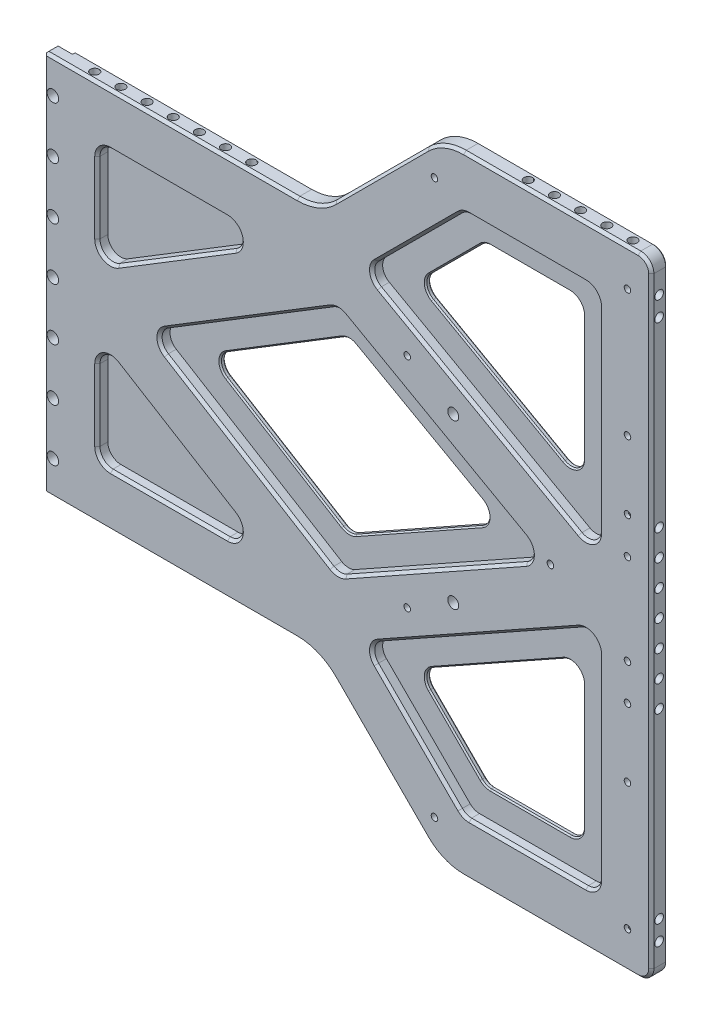
SolidWorks part; units mm, degrees
material "6061 合金"
ref_plane "前视基准面" through (0, 0, 0) normal (0, 0, 1) x (1, 0, 0)
ref_plane "上视基准面" through (0, 0, 0) normal (0, 1, 0) x (1, 0, 0)
ref_plane "右视基准面" through (0, 0, 0) normal (1, 0, 0) x (0, 0, -1)
sketch "草图1" plane through (0, 0, 0) normal (0, 0, 1) x (1, 0, 0)
  line L0 (11.5, -73) -> (-13.5, -73) construction
  line L1 (11.5, 73) -> (110.1759, 73)
  line L2 (11.5, 73) -> (11.5, -73)
  line L3 (11.5, -73) -> (110.1759, -73)
  line L5 (387.1759, 0) -> (237.1759, 0) construction
  line L6 (-812.8241, 0) -> (387.1759, 0) construction
  line L7 (237.1759, 120) -> (237.1759, -120)
  line L8 (237.1759, 120) -> (157.1759, 120)
  line L11 (237.1759, -120) -> (157.1759, -120)
  line L12 (157.1759, 120) -> (110.1759, 73)
  line L13 (157.1759, -120) -> (110.1759, -73)
  point P10 (237.1759, 0)
  point P15 (237.1759, 0)
extrude "凸台-拉伸1" add sketch "草图1" against normal blind 1
sketch "草图2" plane through (0, 0, 0) normal (0, 0, 1) x (1, 0, 0)
  line L0 (11.5, 73) -> (5.5, 73)
  line L1 (5.5, 73) -> (5.5, -73)
  line L2 (5.5, -73) -> (11.5, -73)
  line L8 (11.5, 73) -> (11.5, -73)
  line L9 (11.5, -73) -> (110.1759, -73)
  line L10 (110.1759, -73) -> (157.1759, -120)
  line L11 (157.1759, -120) -> (237.1759, -120)
  line L12 (237.1759, -120) -> (237.1759, 120)
  line L13 (237.1759, 120) -> (157.1759, 120)
  line L14 (157.1759, 120) -> (110.1759, 73)
  line L15 (110.1759, 73) -> (11.5, 73)
  line L16 (11.5, 73) -> (11.5, -73) construction
  line L17 (11.5, -73) -> (110.1759, -73)
  line L18 (110.1759, -73) -> (157.1759, -120)
  line L19 (157.1759, -120) -> (237.1759, -120)
  line L20 (237.1759, -120) -> (237.1759, 120)
  line L21 (237.1759, 120) -> (157.1759, 120)
  line L22 (157.1759, 120) -> (110.1759, 73)
  line L23 (110.1759, 73) -> (11.5, 73)
  dimension "D1" = 0
extrude "凸台-拉伸2" add sketch "草图2" along normal blind 5
fillet "圆角1" radius 20 4 edges at (157.1759, 120, 2) (157.1759, -120, 2) (110.1759, -73, 2) (110.1759, 73, 2)
sketch "草图3" plane through (0, 0, 5) normal (0, 0, 1) x (1, 0, 0)
  line L8 (217.1759, 0) -> (117.1989, 56.0448) construction
  line L9 (217.1759, 0) -> (117.1989, -56.0448) construction
  line L11 (25.5, 0) -> (117.1989, 56.0448) construction
  line L12 (25.5, 0) -> (117.1989, -56.0448) construction
  line L13 (237.6263, 0) -> (116.9806, 67.6312)
  line L14 (6.3243, 0) -> (116.9806, 67.6312)
  line L15 (6.3243, 0) -> (116.9806, -67.6312)
  line L16 (217.1759, 100) -> (165.4601, 100)
  line L17 (165.4601, 100) -> (130.1759, 64.7157)
  line L18 (101.8916, 53) -> (25.5, 53)
  line L19 (25.5, 53) -> (25.5, -53)
  line L20 (25.5, -53) -> (101.8916, -53)
  line L21 (130.1759, -64.7157) -> (165.4601, -100)
  line L22 (165.4601, -100) -> (217.1759, -100)
  line L23 (217.1759, -100) -> (217.1759, 100)
  line L24 (217.1759, 100) -> (165.4601, 100)
  line L25 (165.4601, 100) -> (130.1759, 64.7157)
  line L26 (101.8916, 53) -> (25.5, 53)
  line L27 (25.5, 53) -> (25.5, -53)
  line L28 (25.5, -53) -> (101.8916, -53)
  line L29 (130.1759, -64.7157) -> (165.4601, -100)
  line L30 (165.4601, -100) -> (217.1759, -100)
  line L31 (217.1759, -100) -> (217.1759, 100)
  line L32 (237.6263, 0) -> (116.9806, -67.6312)
  line L33 (196.7254, 0) -> (117.4172, 44.4584)
  line L34 (44.6757, 0) -> (117.4172, 44.4584)
  line L35 (44.6757, 0) -> (117.4172, -44.4584)
  line L36 (196.7254, 0) -> (117.4172, -44.4584)
  arc A8 (101.8916, 53) -> (130.1759, 64.7157) centre (101.8916, 93) ccw
  arc A9 (130.1759, -64.7157) -> (101.8916, -53) centre (101.8916, -93) ccw
  arc A10 (101.8916, 53) -> (130.1759, 64.7157) centre (101.8916, 93) ccw
  arc A11 (130.1759, -64.7157) -> (101.8916, -53) centre (101.8916, -93) ccw
  dimension "D2" = 10
  dimension "D1" = 20
  dimension "D3" = 10
extrude "切除-拉伸1" cut sketch "草图3" against normal blind 4 contours L36 L33 L34 L35 | A10 L13 L31 L24 L25 | A11 L29 L30 L31 L32 | L27 L28 L15 | L26 L27 L14 region at (183.7899, 63.6338, 5) region at (183.7899, -63.6338, 5) region at (48.0138, 39.2399, 5) region at (48.0138, -39.2399, 5) region at (119.6061, 0, 5)
fillet "圆角2" radius 5 18 edges at (165.4601, -100, 3) (217.1759, -100, 3) (217.1759, -11.4641, 3) (127.1113, -61.9522, 3) (217.1759, 11.4641, 3) (165.4601, 100, 3) (127.1113, 61.9522, 3) (117.4172, 44.4584, 3) (44.6757, 0, 3) (117.4172, -44.4584, 3) (196.7254, 0, 3) (25.5, -53, 3) (93.0414, -53, 3) (25.5, -11.7198, 3) (25.5, 53, 3) (25.5, 11.7198, 3) (93.0414, 53, 3) (217.1759, 100, 3)
sketch "草图4" plane through (0, 0, 1) normal (0, 0, 1) x (1, 0, 0)
  line L8 (176.275, 0) -> (117.6355, 32.872)
  line L9 (117.6355, 32.872) -> (63.8513, 0)
  line L10 (63.8513, 0) -> (117.6355, -32.872)
  line L11 (117.6355, -32.872) -> (176.275, 0)
  line L12 (176.275, 0) -> (117.6355, 32.872)
  line L13 (117.6355, 32.872) -> (63.8513, 0)
  line L14 (63.8513, 0) -> (117.6355, -32.872)
  line L15 (117.6355, -32.872) -> (176.275, 0)
  line L19 (143.7124, 64.1101) -> (207.1759, 28.5339)
  line L20 (207.1759, 28.5339) -> (207.1759, 90)
  line L21 (207.1759, 90) -> (169.6023, 90)
  line L22 (169.6023, 90) -> (143.7124, 64.1101)
  line L23 (143.7124, 64.1101) -> (207.1759, 28.5339)
  line L24 (207.1759, 28.5339) -> (207.1759, 90)
  line L25 (207.1759, 90) -> (169.6023, 90)
  line L26 (169.6023, 90) -> (143.7124, 64.1101)
  line L31 (143.7124, -64.1101) -> (169.6023, -90)
  line L32 (169.6023, -90) -> (207.1759, -90)
  line L33 (207.1759, -90) -> (207.1759, -28.5339)
  line L34 (207.1759, -28.5339) -> (143.7124, -64.1101)
  line L35 (143.7124, -64.1101) -> (169.6023, -90)
  line L36 (169.6023, -90) -> (207.1759, -90)
  line L37 (207.1759, -90) -> (207.1759, -28.5339)
  line L38 (207.1759, -28.5339) -> (143.7124, -64.1101)
  dimension "D1" = 10
  dimension "D2" = 10
  dimension "D3" = 10
extrude "切除-拉伸2" cut sketch "草图4" against normal blind 5
fillet "圆角3" radius 5 12 edges at (63.8513, 0, 0) (117.6355, 32.872, 0) (176.275, 0, 0) (117.6355, -32.872, 0) (207.1759, 90, 0) (207.1759, 28.5339, 0) (169.6023, 90, 0) (207.1759, -90, 0) (169.6023, -90, 0) (143.7124, -64.1101, 0) (207.1759, -28.5339, 0) (143.7124, 64.1101, 0)
fillet "圆角4" radius 5 2 edges at (237.1759, 120, 2) (237.1759, -120, 2)
chamfer "倒角1" distance 1 angle 45 36 edges at (26.9645, 51.5355, 5) (25.5, 34.3178, 5) (52.8864, 53, 5) (28.0543, 16.2746, 5) (80.0858, 49.3544, 5) (55.4938, 30.0516, 5) (26.9645, -51.5355, 5) (25.5, -34.3178, 5) (52.8864, -53, 5) (28.0543, -16.2746, 5) (80.0858, -49.3544, 5) (55.4938, -30.0516, 5) (49.2635, 0, 5) (83.2874, 23.5989, 5) (83.2874, -23.5989, 5) (117.4322, 43.6643, 5) (117.4322, -43.6643, 5) (154.4582, 23.694, 5) (154.4582, -23.694, 5) (191.5002, 0, 5) (165.6178, -99.6194, 5) (147.9842, -82.5241, 5) (189.8535, -100, 5) (130.5553, -62.2931, 5) (215.7114, -98.5355, 5) (171.3971, -37.1266, 5) (217.1759, -57.4995, 5) (214.7032, -15.6848, 5) (171.3971, 37.1266, 5) (214.7032, 15.6848, 5) (130.5553, 62.2931, 5) (217.1759, 57.4995, 5) (147.9842, 82.5241, 5) (215.7114, 98.5355, 5) (165.6178, 99.6194, 5) (189.8535, 100, 5)
chamfer "倒角2" distance 1 angle 45 13 edges at (53.6958, 73, 5) (109.5453, 74.5224, 5) (133.6759, 96.5, 5) (53.6958, -73, 5) (157.8065, 118.4776, 5) (109.5453, -74.5224, 5) (198.818, 120, 5) (133.6759, -96.5, 5) (235.7114, 118.5355, 5) (157.8065, -118.4776, 5) (237.1759, 0, 5) (198.818, -120, 5) (235.7114, -118.5355, 5)
sketch "草图5" plane through (0, 0, 5) normal (0, 0, 1) x (1, 0, 0)
  circle A0 centre (8.5, 60) radius 2.2
  circle A1 centre (8.5, 40) radius 2.2
  circle A2 centre (8.5, 20) radius 2.2
  circle A3 centre (8.5, 0) radius 2.2
  circle A4 centre (8.5, -20) radius 2.2
  circle A5 centre (8.5, -40) radius 2.2
  circle A6 centre (8.5, -60) radius 2.2
  point P0 (8.5, 60)
  point P1 (8.5, 40)
  point P3 (8.5, 20)
  point P5 (8.5, 0)
  point P7 (8.5, -20)
  point P9 (8.5, -40)
  point P11 (8.5, -60)
  dimension "D1" = 7
extrude "切除-拉伸3" cut sketch "草图5" against normal through all both and the other way through all
hole_wizard "M4 螺纹孔1" positions "草图7" profile "草图8" tap size "M4" standard "GB"
sketch "草图7" plane through (0, -73, 0) normal (0, -1, 0) x (-1, 0, 0)
  point P0 (-81.5, -2)
  point P3 (-71.5, -2)
  point P6 (-61.5, -2)
  point P9 (-51.5, -2)
  point P12 (-41.5, -2)
  point P15 (-31.5, -2)
  point P18 (-21.5, -2)
sketch "草图8" plane through (81.5, -73, 2) normal (1, 0, 0) x (0, 0, -1)
  line L0 (0, 0) -> (0, 11.0914)
  line L1 (0, 11.0914) -> (1.65, 10.1)
  line L2 (1.65, 10.1) -> (1.65, 0)
  line L5 (1.65, 0) -> (0, 0)
  line L10 (0, 11.0914) -> (-1.65, 10.1) construction
  line L11 (0, -6.35) -> (0, 107.95) construction
  dimension "螺纹孔钻头直径" = 3.3
  dimension "螺纹孔钻头深度" = 10.1
  dimension "导头角度" = 118
cosmetic thread "孔螺蚊线1" parameters "D1"=8, "D2"=4
cosmetic thread "孔螺蚊线2" parameters "D1"=8, "D2"=4
cosmetic thread "孔螺蚊线3" parameters "D1"=8, "D2"=4
cosmetic thread "孔螺蚊线4" parameters "D1"=8, "D2"=4
cosmetic thread "孔螺蚊线5" parameters "D1"=8, "D2"=4
cosmetic thread "孔螺蚊线6" parameters "D1"=8, "D2"=4
cosmetic thread "孔螺蚊线7" parameters "D1"=8, "D2"=4
mirror "镜向1" about plane through (0, 0, 0) normal (0, 1, 0) of "M4 螺纹孔1"
cosmetic thread "孔螺蚊线8" parameters "D1"=8, "D2"=4
cosmetic thread "孔螺蚊线9" parameters "D1"=8, "D2"=4
cosmetic thread "孔螺蚊线10" parameters "D1"=8, "D2"=4
cosmetic thread "孔螺蚊线11" parameters "D1"=8, "D2"=4
cosmetic thread "孔螺蚊线12" parameters "D1"=8, "D2"=4
cosmetic thread "孔螺蚊线13" parameters "D1"=8, "D2"=4
cosmetic thread "孔螺蚊线14" parameters "D1"=8, "D2"=4
hole_wizard "M4 螺纹孔2" positions "草图10" profile "草图11" tap size "M4" standard "GB"
sketch "草图10" plane through (0, -120, 0) normal (0, -1, 0) x (-1, 0, 0)
  point P0 (-227.1759, -2)
  point P3 (-217.1759, -2)
  point P6 (-207.1759, -2)
  point P9 (-197.1759, -2)
  point P12 (-187.1759, -2)
sketch "草图11" plane through (227.1759, -120, 2) normal (1, 0, 0) x (0, 0, -1)
  line L0 (0, 0) -> (0, 11.0914)
  line L1 (0, 11.0914) -> (1.65, 10.1)
  line L2 (1.65, 10.1) -> (1.65, 0)
  line L5 (1.65, 0) -> (0, 0)
  line L10 (0, 11.0914) -> (-1.65, 10.1) construction
  line L11 (0, -6.35) -> (0, 107.95) construction
  dimension "螺纹孔钻头直径" = 3.3
  dimension "螺纹孔钻头深度" = 10.1
  dimension "导头角度" = 118
cosmetic thread "孔螺蚊线15" parameters "D1"=8, "D2"=4
cosmetic thread "孔螺蚊线16" parameters "D1"=8, "D2"=4
cosmetic thread "孔螺蚊线17" parameters "D1"=8, "D2"=4
cosmetic thread "孔螺蚊线18" parameters "D1"=8, "D2"=4
cosmetic thread "孔螺蚊线19" parameters "D1"=8, "D2"=4
mirror "镜向2" about plane through (0, 0, 0) normal (0, 1, 0) of "M4 螺纹孔2"
cosmetic thread "孔螺蚊线20" parameters "D1"=8, "D2"=4
cosmetic thread "孔螺蚊线21" parameters "D1"=8, "D2"=4
cosmetic thread "孔螺蚊线22" parameters "D1"=8, "D2"=4
cosmetic thread "孔螺蚊线23" parameters "D1"=8, "D2"=4
cosmetic thread "孔螺蚊线24" parameters "D1"=8, "D2"=4
hole_wizard "M4 螺纹孔3" positions "草图13" profile "草图14" tap size "M4" standard "GB"
sketch "草图13" plane through (237.1759, 0, 0) normal (1, 0, 0) x (0, 0, -1)
  point P0 (-2, -99.5)
  point P3 (-2, -107)
sketch "草图14" plane through (237.1759, -99.5, 2) normal (0, 1, 0) x (0, 0, -1)
  line L0 (0, 0) -> (0, 11.0914)
  line L1 (0, 11.0914) -> (1.65, 10.1)
  line L2 (1.65, 10.1) -> (1.65, 0)
  line L5 (1.65, 0) -> (0, 0)
  line L10 (0, 11.0914) -> (-1.65, 10.1) construction
  line L11 (0, -6.35) -> (0, 107.95) construction
  dimension "螺纹孔钻头直径" = 3.3
  dimension "螺纹孔钻头深度" = 10.1
  dimension "导头角度" = 118
cosmetic thread "孔螺蚊线26" parameters "D1"=8, "D2"=4
cosmetic thread "孔螺蚊线27" parameters "D1"=8, "D2"=4
mirror "镜向3" about plane through (0, 0, 0) normal (0, 1, 0) of "M4 螺纹孔3"
cosmetic thread "孔螺蚊线28" parameters "D1"=8, "D2"=4
cosmetic thread "孔螺蚊线29" parameters "D1"=8, "D2"=4
sketch "草图15" plane through (0, 0, 5) normal (0, 0, 1) x (1, 0, 0)
  line L0 (151.5, 0) -> (161.5, 0) construction
  line L1 (151.5, 70) -> (151.5, -70) construction
  line L2 (-812.8241, 0) -> (387.1759, 0) construction
  line L3 (133.4954, -36.5917) -> (142.2972, -52.293) construction
  line L4 (189.4341, -5.2337) -> (120.4603, -43.8989) construction
  line L5 (132.5744, -57.7433) -> (209.2419, -14.7652) construction
  line L6 (89.7964, -71.4061) -> (185.9962, -17.4786) construction
  line L7 (161.5, 31.2106) -> (161.5, -31.2106) construction
  point P15 (137.8963, -44.4423)
  point P18 (161.5, 0)
hole_wizard "M5 螺纹孔1" positions "草图16" profile "草图17" tap size "M5" standard "GB"
sketch "草图16" plane through (0, 0, 5) normal (0, 0, 1) x (1, 0, 0)
  point P0 (161.5, 31.2106)
  point P3 (161.5, -31.2106)
sketch "草图17" plane through (161.5, 31.2106, 5) normal (1, 0, 0) x (0, -1, 0)
  line L0 (0, 0) -> (0, 13.6618)
  line L1 (0, 13.6618) -> (2.1, 12.4)
  line L2 (2.1, 12.4) -> (2.1, 0)
  line L5 (2.1, 0) -> (0, 0)
  line L10 (0, 13.6618) -> (-2.1, 12.4) construction
  line L11 (0, -6.35) -> (0, 107.95) construction
  dimension "螺纹孔钻头直径" = 4.2
  dimension "螺纹孔钻头深度" = 12.4
  dimension "导头角度" = 118
cosmetic thread "孔螺蚊线30" parameters "D1"=10, "D2"=5
cosmetic thread "孔螺蚊线31" parameters "D1"=10, "D2"=5
sketch "草图18" plane through (237.1759, 0, 0) normal (1, 0, 0) x (0, 0, -1)
  line L0 (1, 0) -> (-5, 0) construction
  line L1 (1, -115) -> (1, 115) construction
  line L2 (-2, 10) -> (-2, -10) construction
  line L3 (-2, 20) -> (-2, -20) construction
  line L4 (-2, 30) -> (-2, -30) construction
  point P8 (-2, 0)
  point P12 (-2, 0)
  point P15 (-2, 0)
hole_wizard "M4 螺纹孔4" positions "草图19" profile "草图20" tap size "M4" standard "GB"
sketch "草图19" plane through (237.1759, 0, 0) normal (1, 0, 0) x (0, 0, -1)
  line L0 (-2, 10) -> (-2, -10) construction
  point P0 (-2, 30)
  point P3 (-2, 20)
  point P6 (-2, 10)
  point P9 (-2, 0)
  point P13 (-2, -10)
  point P16 (-2, -20)
  point P19 (-2, -30)
sketch "草图20" plane through (237.1759, 30, 2) normal (0, 1, 0) x (0, 0, -1)
  line L0 (0, 0) -> (0, 11.0914)
  line L1 (0, 11.0914) -> (1.65, 10.1)
  line L2 (1.65, 10.1) -> (1.65, 0)
  line L5 (1.65, 0) -> (0, 0)
  line L10 (0, 11.0914) -> (-1.65, 10.1) construction
  line L11 (0, -6.35) -> (0, 107.95) construction
  dimension "螺纹孔钻头直径" = 3.3
  dimension "螺纹孔钻头深度" = 10.1
  dimension "导头角度" = 118
cosmetic thread "孔螺蚊线32" parameters "D1"=8, "D2"=4
cosmetic thread "孔螺蚊线33" parameters "D1"=8, "D2"=4
cosmetic thread "孔螺蚊线34" parameters "D1"=8, "D2"=4
cosmetic thread "孔螺蚊线35" parameters "D1"=8, "D2"=4
cosmetic thread "孔螺蚊线36" parameters "D1"=8, "D2"=4
cosmetic thread "孔螺蚊线37" parameters "D1"=8, "D2"=4
cosmetic thread "孔螺蚊线38" parameters "D1"=8, "D2"=4
sketch "草图21" plane through (0, 0, 5) normal (0, 0, 1) x (1, 0, 0)
  line L0 (161.5, -31.2106) -> (143.9, -31.2106)
  line L1 (143.9, -31.2106) -> (143.9, -41.7006)
  line L3 (161.5, -31.2106) -> (161.5, -105.8306)
  line L4 (161.5, -105.8306) -> (154.33, -105.8306)
  line L5 (161.5, -31.2106) -> (198.64, -31.2106)
  line L6 (198.64, -31.2106) -> (198.64, -0.0706)
  line L7 (228.08, -31.2106) -> (228.08, -17.3206)
  line L8 (198.64, -31.2106) -> (228.08, -31.2106)
  line L9 (228.08, -31.2106) -> (228.08, -57.3206)
  line L10 (228.08, -57.3206) -> (228.08, -105.8406)
hole_wizard "M3 螺纹孔1" positions "草图22" profile "草图23" tap size "M3" standard "GB"
sketch "草图22" plane through (0, 0, 5) normal (0, 0, 1) x (1, 0, 0)
  point P0 (143.9, -41.7006)
  point P3 (154.33, -105.8306)
  point P6 (198.64, 0.0706)
  point P8 (228.08, -31.2106)
  point P11 (228.08, -17.3206)
  point P14 (228.08, -105.8406)
  point P17 (228.08, -57.3206)
sketch "草图23" plane through (143.9, -41.7006, 5) normal (1, 0, 0) x (0, -1, 0)
  line L0 (0, 0) -> (0, 8.2511)
  line L1 (0, 8.2511) -> (1.25, 7.5)
  line L2 (1.25, 7.5) -> (1.25, 0)
  line L5 (1.25, 0) -> (0, 0)
  line L10 (0, 8.2511) -> (-1.25, 7.5) construction
  line L11 (0, -6.35) -> (0, 107.95) construction
  dimension "螺纹孔钻头直径" = 2.5
  dimension "螺纹孔钻头深度" = 7.5
  dimension "导头角度" = 118
cosmetic thread "孔螺蚊线39" parameters "D1"=6, "D2"=3
cosmetic thread "孔螺蚊线40" parameters "D1"=6, "D2"=3
cosmetic thread "孔螺蚊线41" parameters "D1"=6, "D2"=3
cosmetic thread "孔螺蚊线42" parameters "D1"=6, "D2"=3
cosmetic thread "孔螺蚊线43" parameters "D1"=6, "D2"=3
cosmetic thread "孔螺蚊线44" parameters "D1"=6, "D2"=3
cosmetic thread "孔螺蚊线45" parameters "D1"=6, "D2"=3
mirror "镜向4" about plane through (0, 0, 0) normal (0, 1, 0) of "M3 螺纹孔1"
cosmetic thread "孔螺蚊线46" parameters "D1"=6, "D2"=3
cosmetic thread "孔螺蚊线47" parameters "D1"=6, "D2"=3
cosmetic thread "孔螺蚊线48" parameters "D1"=6, "D2"=3
cosmetic thread "孔螺蚊线49" parameters "D1"=6, "D2"=3
cosmetic thread "孔螺蚊线50" parameters "D1"=6, "D2"=3
cosmetic thread "孔螺蚊线51" parameters "D1"=6, "D2"=3
cosmetic thread "孔螺蚊线52" parameters "D1"=6, "D2"=3
chamfer "倒角3" distance 0.5 angle 45 48 edges at (92.9844, -17.8057, -1) (117.6504, -32.0779, -1) (68.4391, 0, -1) (144.3421, -17.9008, -1) (92.9844, 17.8057, -1) (171.0497, 0, -1) (117.6504, 32.0779, -1) (144.3421, 17.9008, -1) (92.9844, -17.8057, 1) (117.6504, -32.0779, 1) (68.4391, 0, 1) (144.3421, -17.9008, 1) (92.9844, 17.8057, 1) (171.0497, 0, 1) (117.6504, 32.0779, 1) (144.3421, 17.9008, 1) (146.9635, 64.5591, 1) (158.2594, 78.6571, 1) (174.6012, 46.7945, 1) (169.7599, 89.6194, 1) (204.7032, 32.7546, 1) (186.9246, 90, 1) (207.1759, 61.0344, 1) (205.7114, 88.5355, 1) (146.9635, 64.5591, -1) (174.6012, 46.7945, -1) (158.2594, 78.6571, -1) (204.7032, 32.7546, -1) (169.7599, 89.6194, -1) (207.1759, 61.0344, -1) (186.9246, 90, -1) (205.7114, 88.5355, -1) (169.7599, -89.6194, 1) (158.2594, -78.6571, 1) (186.9246, -90, 1) (146.9635, -64.5591, 1) (205.7114, -88.5355, 1) (174.6012, -46.7945, 1) (207.1759, -61.0344, 1) (204.7032, -32.7546, 1) (169.7599, -89.6194, -1) (186.9246, -90, -1) (158.2594, -78.6571, -1) (205.7114, -88.5355, -1) (146.9635, -64.5591, -1) (207.1759, -61.0344, -1) (174.6012, -46.7945, -1) (204.7032, -32.7546, -1)
chamfer "倒角4" distance 0.5 angle 45 18 edges at (56.6958, -73, -1) (109.5453, -74.5224, -1) (133.6759, -96.5, -1) (157.8065, -118.4776, -1) (198.818, -120, -1) (235.7114, -118.5355, -1) (237.1759, 0, -1) (235.7114, 118.5355, -1) (198.818, 120, -1) (157.8065, 118.4776, -1) (133.6759, 96.5, -1) (109.5453, 74.5224, -1) (56.6958, 73, -1) (8.5, -73, 0) (8.5, 73, 0) (5.5, 73, 2) (5.5, 0, 0) (5.5, -73, 2)
chamfer "倒角5" distance 0.5 angle 45 1 edges at (5.5, 0, 5)
